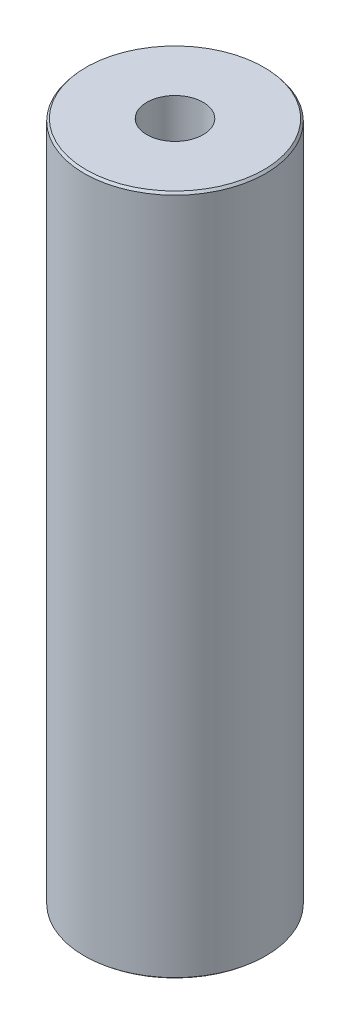
SolidWorks part; units mm, degrees
ref_plane "Front Plane" through (0, 0, 0) normal (0, 0, 1) x (1, 0, 0)
ref_plane "Top Plane" through (0, 0, 0) normal (0, 1, 0) x (1, 0, 0)
ref_plane "Right Plane" through (0, 0, 0) normal (1, 0, 0) x (0, 0, -1)
sketch "Sketch1" plane through (0, 0, 0) normal (0, 1, 0) x (1, 0, 0)
  circle A0 centre (0, 0) radius 55
  dimension "SHAFT_OD" = 110
extrude "Boss-Extrude1" add sketch "Sketch1" along normal blind 413.1831
sketch "Sketch2" plane through (0, 0, 0) normal (0, 1, 0) x (1, 0, 0)
  circle A0 centre (0, 0) radius 17.064
  dimension "BORE_D" = 34.128
extrude "Cut-Extrude1" cut sketch "Sketch2" along normal through all
chamfer "Chamfer1" distance 1.3774 angle 39.795 2 edges at (0, 413.1831, 55) (0, 0, 55) first distance on face at (0, 413.1831, 55) first distance on face at (0, 0, 17.064)
